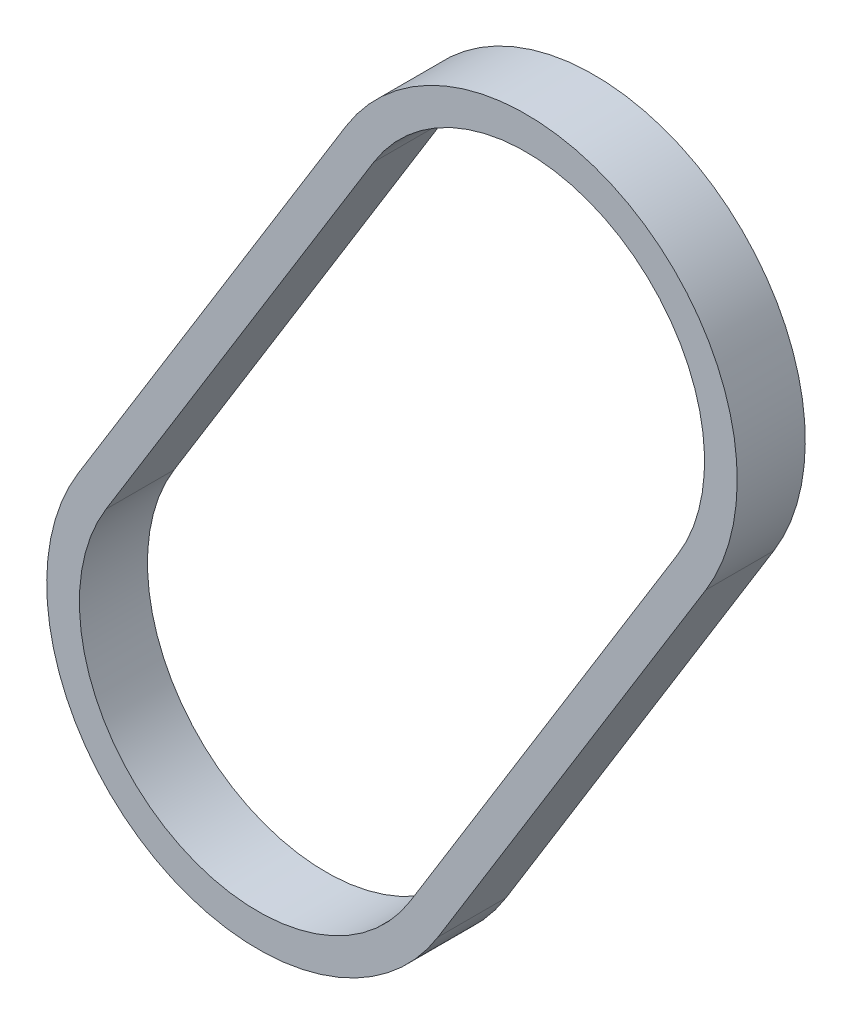
SolidWorks part; units mm, degrees
material "Rubber"
ref_plane "Front Plane" through (0, 0, 0) normal (0, 0, 1) x (1, 0, 0)
ref_plane "Top Plane" through (0, 0, 0) normal (0, 1, 0) x (1, 0, 0)
ref_plane "Right Plane" through (0, 0, 0) normal (1, 0, 0) x (0, 0, -1)
sketch "Sketch2" plane through (0, 0, 0) normal (0, 0, 1) x (1, 0, 0)
  line L0 (0, 0) -> (1, 0) construction
  line L1 (0, 0) -> (0, 1) construction
  line L2 (31.8706, 24.4068) -> (12.1936, -7.516)
  line L3 (-12.1936, 7.516) -> (7.4833, 39.4389)
  arc A0 (7.4833, 39.4389) -> (31.8706, 24.4068) centre (19.6769, 31.9229) cw
  arc A1 (12.1936, -7.516) -> (-12.1936, 7.516) centre (0, 0) cw
extrude "Extrude-Thin1" add sketch "Sketch2" against normal blind 5 thin thin type two direction wall 1.2 second wall 1.2
